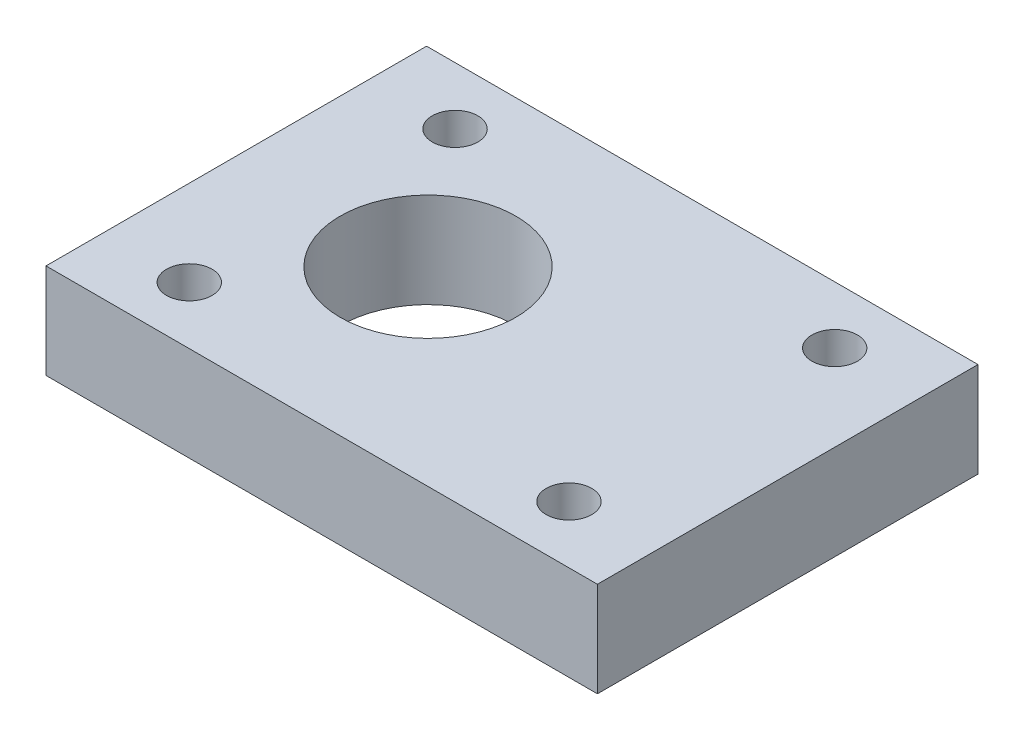
SolidWorks part; units mm, degrees
ref_plane "Front Plane" through (0, 0, 0) normal (0, 0, 1) x (1, 0, 0)
ref_plane "Top Plane" through (0, 0, 0) normal (0, 1, 0) x (1, 0, 0)
ref_plane "Right Plane" through (0, 0, 0) normal (1, 0, 0) x (0, 0, -1)
sketch "Sketch1" plane through (0, 0, 0) normal (0, 1, 0) x (1, 0, 0)
  line L0 (69.2296, 24.1084) -> (31.3296, 24.1084) construction
  line L5 (20.1796, 10.1084) -> (60.1796, 10.1084)
  line L6 (20.1796, 10.1084) -> (20.1796, 38.1084)
  line L7 (20.1796, 38.1084) -> (60.1796, 38.1084)
  line L8 (60.1796, 10.1084) -> (60.1796, 38.1084)
  line L9 (11.1296, 4.0584) -> (69.2296, 4.0584)
  line L10 (11.1296, 4.0584) -> (11.1296, 44.1584)
  line L11 (11.1296, 44.1584) -> (69.2296, 44.1584)
  line L12 (69.2296, 4.0584) -> (69.2296, 44.1584)
  circle A0 centre (20.1796, 38.1084) radius 2.4
  circle A1 centre (60.1796, 38.1084) radius 2.4
  circle A2 centre (20.1796, 10.1084) radius 2.4
  circle A3 centre (60.1796, 10.1084) radius 2.4
  circle A4 centre (31.3296, 24.1084) radius 9.25
  circle A5 centre (20.1796, 38.1084) radius 4
  circle A6 centre (60.1796, 38.1084) radius 4
  circle A7 centre (60.1796, 10.1084) radius 4
  circle A8 centre (20.1796, 10.1084) radius 4
  point P19 (0, 0)
  point P20 (0, 0)
  dimension "D5" = 4.8
  dimension "D6" = 4.8
  dimension "D7" = 4.8
  dimension "D8" = 4.8
  dimension "D9" = 9.05
  dimension "D14" = 18.5
  dimension "D15" = 8
  dimension "D16" = 8
  dimension "D17" = 8
  dimension "D18" = 8
  dimension "D1" = 40.1
  dimension "D2" = 58.1
  dimension "D3" = 28
  dimension "D4" = 40
  dimension "D10" = 9.05
  dimension "D11" = 6.05
  dimension "D12" = 6.05
  dimension "D13" = 37.9
extrude "Boss-Extrude1" add sketch "Sketch1" along normal blind 10 contours L12 L11 L10 L9
extrude "Cut-Extrude1" cut sketch "Sketch1<7>" along normal blind 10 contours A4
sketch "Sketch1<7>" plane through (0, 0, 0) normal (0, 1, 0) x (1, 0, 0) same geometry as "Sketch1"
extrude "Cut-Extrude2" cut sketch "Sketch1<8>" along normal blind 10 contours A0 | A2 | A3 | A1
sketch "Sketch1<8>" plane through (0, 0, 0) normal (0, 1, 0) x (1, 0, 0) same geometry as "Sketch1"
